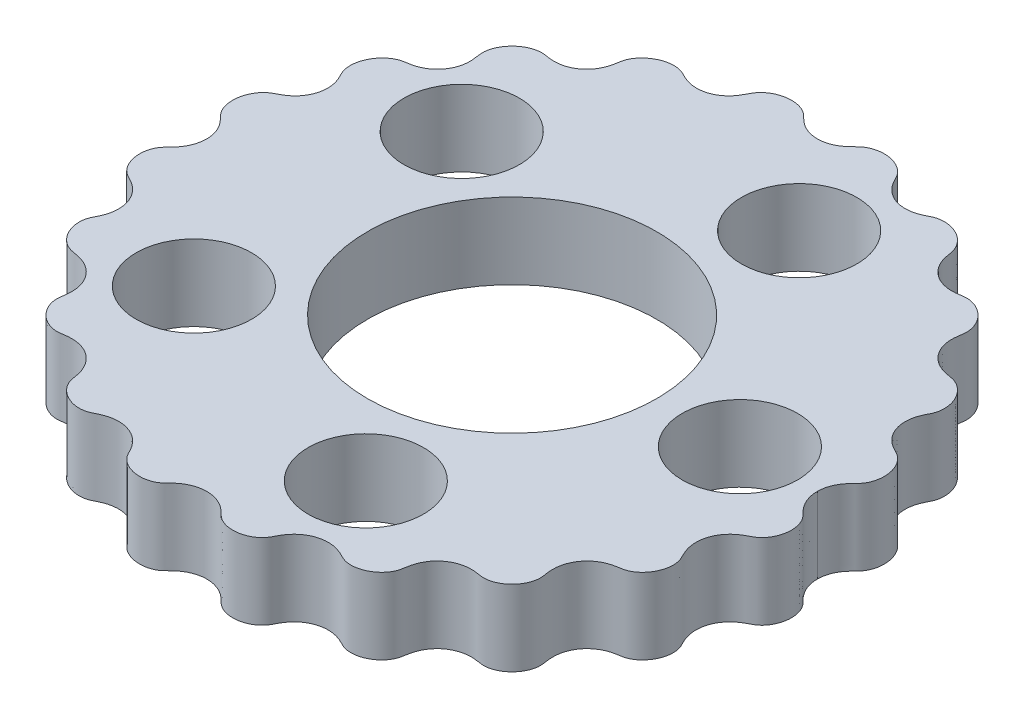
SolidWorks part; units mm, degrees
ref_plane "Front Plane" through (0, 0, 0) normal (0, 0, 1) x (1, 0, 0)
ref_plane "Top Plane" through (0, 0, 0) normal (0, 1, 0) x (1, 0, 0)
ref_plane "Right Plane" through (0, 0, 0) normal (1, 0, 0) x (0, 0, -1)
sketch "MAIN" plane through (0, 0, 0) normal (0, 1, 0) x (1, 0, 0)
  line L0 (-20.1, 0) -> (20.1, 0) construction
  line L1 (0, 0) -> (-0.8, 0)
  line L4 (0, -20.1) -> (0, 20.1) construction
  line L5 (-0.8, -20.2489) -> (-0.8, 20.2572) construction
  circle A22 centre (0, 0) radius 15
  circle A23 centre (15, 0) radius 3.8
  circle A24 centre (4.6353, -14.2658) radius 3.8
  circle A25 centre (-12.1353, -8.8168) radius 3.8
  circle A26 centre (-12.1353, 8.8168) radius 3.8
  circle A27 centre (4.6353, 14.2658) radius 3.8
  circle A29 centre (0, 0) radius 9.525
  spline S0 degree 4 poles (20.5886, 4.7068) (20.68, 4.6551) (20.8532, 4.5348) (21.1393, 4.2364) (21.3748, 3.7649) (21.4816, 3.2447) (21.4517, 2.7569) (21.3623, 2.4139) (21.2306, 2.1338) (21.0766, 1.9171) (20.8954, 1.7433) (20.7304, 1.5739) (20.553, 1.3627) (20.4068, 1.1453) (20.2874, 0.911) (20.1977, 0.6657) (20.1512, 0.4864) (20.1234, 0.3358) (20.1091, 0.21) (20.1026, 0.1123) (20.0996, 0.0252) (20.0999, -0.045) (20.1041, -0.1445) (20.1129, -0.2489) (20.1295, -0.3715) (20.1582, -0.5159) (20.2042, -0.6849) (20.2735, -0.8706) (20.3588, -1.0503) (20.459, -1.2218) (20.5666, -1.3754) (20.6778, -1.5121) (20.7891, -1.634) (20.8973, -1.7433) (21.0065, -1.8517) (21.1088, -1.9667) (21.2202, -2.1239) (21.3466, -2.3693) (21.4488, -2.7149) (21.4796, -3.1509) (21.4067, -3.6189) (21.2535, -4.0101) (21.0548, -4.3168) (20.8346, -4.5468) (20.6123, -4.7043) (20.3253, -4.8398) (20.0085, -5.0187) (19.6843, -5.2734) (19.3864, -5.6226) (19.1654, -6.0238) (19.0313, -6.4606) (18.9938, -6.8578) (19.019, -7.1969) (19.0763, -7.4737) (19.1428, -7.6897) (19.2312, -7.9077) (19.34, -8.1256) (19.4583, -8.3497) (19.5343, -8.602) (19.5712, -8.9102) (19.5475, -9.2683) (19.4413, -9.6634) (19.2307, -10.0711) (18.9626, -10.3939) (18.6946, -10.6074) (18.4633, -10.7327) (18.291, -10.7987) (18.1484, -10.8366) (18.0032, -10.862) (17.8576, -10.8843) (17.6411, -10.9233) (17.3574, -10.9968) (17.0179, -11.137) (16.6499, -11.3793) (16.3344, -11.6905) (16.085, -12.0601) (15.9134, -12.4744) (15.8373, -12.8617) (15.8261, -13.1985) (15.849, -13.4869) (15.8867, -13.7254) (15.9272, -13.9735) (15.9178, -14.2345) (15.8554, -14.5357) (15.7209, -14.8652) (15.4941, -15.2104) (15.1574, -15.5384) (14.7814, -15.7682) (14.4318, -15.8866) (14.1468, -15.9236) (13.9404, -15.918) (13.777, -15.8957) (13.5739, -15.8619) (13.3114, -15.8302) (12.9878, -15.8261) (12.6091, -15.8813) (12.2295, -16.0072) (11.877, -16.1993) (11.5634, -16.4525) (11.2997, -16.7592) (11.0942, -17.1092) (10.963, -17.4616) (10.8972, -17.764) (10.8626, -18.0051) (10.8228, -18.2154) (10.7561, -18.4196) (10.6183, -18.6831) (10.379, -18.9781) (10.0502, -19.2452) (9.6329, -19.4535) (9.2235, -19.5558) (8.8836, -19.5696) (8.6248, -19.5345) (8.4481, -19.4868) (8.3117, -19.4338) (8.1804, -19.3695) (8.0505, -19.3025) (7.8489, -19.2051) (7.5676, -19.0948) (7.1959, -19.0078) (6.7361, -18.9938) (6.2861, -19.0732) (5.8648, -19.241) (5.4886, -19.4879) (5.2101, -19.7619) (5.0117, -20.0304) (4.884, -20.2493) (4.8047, -20.4037) (4.7227, -20.5647) (4.6271, -20.7269) (4.4866, -20.8967) (4.2614, -21.0946) (3.9625, -21.275) (3.5833, -21.4148) (3.129, -21.4789) (2.7059, -21.4461) (2.3697, -21.3462) (2.1288, -21.223) (1.9722, -21.1131) (1.8575, -21.0121) (1.7229, -20.8767) (1.5347, -20.6912) (1.271, -20.4785) (0.9112, -20.275) (0.4846, -20.1344) (0.0431, -20.0821) (-0.3958, -20.1176) (-0.8148, -20.2365) (-1.152, -20.4058) (-1.4146, -20.5926) (-1.6227, -20.7757) (-1.7854, -20.9409) (-1.9581, -21.1102) (-2.1683, -21.2484) (-2.4378, -21.3695) (-2.7687, -21.4523) (-3.1582, -21.4754) (-3.5925, -21.4114) (-3.9625, -21.275) (-4.2614, -21.0946) (-4.4866, -20.8967) (-4.6271, -20.7269) (-4.7227, -20.5647) (-4.8047, -20.4037) (-4.884, -20.2493) (-5.0117, -20.0304) (-5.2101, -19.7619) (-5.4886, -19.4879) (-5.8648, -19.241) (-6.2861, -19.0732) (-6.7361, -18.9938) (-7.1959, -19.0078) (-7.5676, -19.0948) (-7.8489, -19.2051) (-8.0505, -19.3025) (-8.1804, -19.3695) (-8.3117, -19.4338) (-8.4481, -19.4868) (-8.6248, -19.5345) (-8.8836, -19.5696) (-9.2235, -19.5558) (-9.6329, -19.4535) (-10.0502, -19.2452) (-10.379, -18.9781) (-10.6183, -18.6831) (-10.7561, -18.4196) (-10.8228, -18.2154) (-10.8561, -18.0402) (-10.8777, -17.8992) (-10.9125, -17.6942) (-10.9754, -17.428) (-11.0942, -17.1093) (-11.2996, -16.7592) (-11.5634, -16.4525) (-11.877, -16.1993) (-12.2295, -16.0072) (-12.6091, -15.8813) (-12.9878, -15.8261) (-13.3114, -15.8302) (-13.5739, -15.8619) (-13.777, -15.8957) (-13.9404, -15.918) (-14.1468, -15.9236) (-14.4318, -15.8866) (-14.7814, -15.7682) (-15.1574, -15.5384) (-15.4941, -15.2104) (-15.7209, -14.8652) (-15.8554, -14.5357) (-15.9178, -14.2345) (-15.9272, -13.9735) (-15.8867, -13.7254) (-15.849, -13.4869) (-15.8261, -13.1985) (-15.8373, -12.8617) (-15.9134, -12.4744) (-16.085, -12.0601) (-16.3344, -11.6905) (-16.6499, -11.3793) (-17.0179, -11.137) (-17.3574, -10.9968) (-17.6411, -10.9233) (-17.8576, -10.8843) (-18.0032, -10.862) (-18.1484, -10.8366) (-18.291, -10.7987) (-18.4633, -10.7327) (-18.6946, -10.6074) (-18.9626, -10.3939) (-19.2307, -10.0711) (-19.4413, -9.6634) (-19.5475, -9.2683) (-19.5712, -8.9102) (-19.5343, -8.602) (-19.4583, -8.3497) (-19.34, -8.1256) (-19.2312, -7.9077) (-19.1215, -7.6374) (-19.0312, -7.3099) (-18.9886, -6.9144) (-19.0312, -6.4607) (-19.1654, -6.0238) (-19.3864, -5.6226) (-19.6843, -5.2734) (-20.0085, -5.0187) (-20.3253, -4.8398) (-20.6123, -4.7043) (-20.8346, -4.5468) (-21.0548, -4.3168) (-21.2535, -4.0101) (-21.4067, -3.6189) (-21.4796, -3.1509) (-21.4488, -2.7149) (-21.3466, -2.3693) (-21.2202, -2.1239) (-21.1088, -1.9667) (-21.0065, -1.8517) (-20.8973, -1.7433) (-20.7891, -1.634) (-20.6778, -1.5121) (-20.5666, -1.3754) (-20.459, -1.2218) (-20.3588, -1.0503) (-20.2735, -0.8706) (-20.2042, -0.6849) (-20.1582, -0.5159) (-20.1295, -0.3715) (-20.1129, -0.2489) (-20.1041, -0.1442) (-20.099, -0.0256) (-20.0999, 0.0597) (-20.107, 0.1917) (-20.1234, 0.3359) (-20.1512, 0.4864) (-20.1977, 0.6656) (-20.2874, 0.9112) (-20.4306, 1.1918) (-20.6222, 1.4599) (-20.8576, 1.7072) (-21.0766, 1.917) (-21.2306, 2.1338) (-21.3623, 2.4139) (-21.4517, 2.7569) (-21.4816, 3.2446) (-21.3748, 3.7649) (-21.1393, 4.2364) (-20.8532, 4.5348) (-20.68, 4.6551) (-20.5886, 4.7068) knots 0 0 0 0 0 0.004854 0.009708 0.018897 0.023991 0.029085 0.03214 0.035194 0.038248 0.041303 0.043723 0.046143 0.050984 0.053404 0.055825 0.058245 0.059455 0.060665 0.061539 0.062412 0.06356 0.064708 0.065855 0.067003 0.069298 0.071593 0.073888 0.076184 0.078479 0.080774 0.082553 0.084332 0.086111 0.08789 0.089668 0.091447 0.095005 0.100606 0.106208 0.111478 0.116748 0.119878 0.123007 0.126137 0.129267 0.13454 0.139813 0.145086 0.150359 0.155581 0.160804 0.163415 0.166026 0.168637 0.171249 0.174275 0.177302 0.180329 0.183356 0.188577 0.193798 0.19911 0.204423 0.207831 0.209535 0.211238 0.212942 0.214646 0.21635 0.218053 0.223116 0.228179 0.233242 0.238305 0.243486 0.248667 0.253849 0.25644 0.25903 0.262031 0.265031 0.268031 0.271032 0.27621 0.281388 0.286995 0.292602 0.296412 0.298318 0.300223 0.302128 0.304034 0.307844 0.312446 0.317047 0.321648 0.32625 0.330919 0.335589 0.340258 0.344928 0.348227 0.349876 0.351526 0.354825 0.358123 0.363551 0.368978 0.374256 0.379533 0.382914 0.384604 0.386294 0.387984 0.389675 0.391365 0.393055 0.39834 0.403624 0.408909 0.414194 0.419326 0.424458 0.429589 0.432155 0.434721 0.43617 0.437618 0.440515 0.443412 0.44631 0.451439 0.456568 0.46197 0.467372 0.470904 0.47267 0.474436 0.476202 0.477968 0.4815 0.486659 0.491818 0.496977 0.502136 0.507093 0.51205 0.517007 0.519485 0.521964 0.524855 0.527745 0.530636 0.533527 0.538479 0.543432 0.548561 0.55369 0.556588 0.559485 0.562382 0.56383 0.565279 0.567845 0.570411 0.575542 0.580674 0.585806 0.591091 0.596376 0.60166 0.606945 0.608635 0.610325 0.612016 0.613706 0.615396 0.617086 0.620467 0.625744 0.631022 0.636449 0.641877 0.645175 0.648474 0.650124 0.651773 0.653423 0.655072 0.659742 0.664411 0.669081 0.67375 0.678352 0.682953 0.687554 0.692156 0.695966 0.697872 0.699777 0.701682 0.703588 0.707398 0.713005 0.718612 0.72379 0.728968 0.731969 0.734969 0.737969 0.74097 0.74356 0.746151 0.751333 0.756514 0.761695 0.766758 0.771821 0.776884 0.781947 0.78365 0.785354 0.787058 0.788762 0.790465 0.792169 0.795577 0.80089 0.806202 0.811423 0.816644 0.819671 0.822698 0.825725 0.828751 0.831363 0.833974 0.839196 0.844419 0.849641 0.854914 0.860187 0.86546 0.870733 0.873863 0.876993 0.880122 0.883252 0.888522 0.893792 0.899394 0.904995 0.908553 0.910332 0.91211 0.913889 0.915668 0.917447 0.919226 0.921521 0.923816 0.926112 0.928407 0.930702 0.932997 0.934145 0.935292 0.93644 0.937588 0.939335 0.940545 0.941755 0.944175 0.946596 0.949016 0.953857 0.958697 0.961752 0.964806 0.96786 0.970915 0.976009 0.981103 0.990292 0.995146 1 1 1 1 1 construction
  spline S1 degree 4 poles (20.1, 0) (20.1, -0.0217) (20.1007, -0.0652) (20.1041, -0.1445) (20.1129, -0.2489) (20.1295, -0.3715) (20.1582, -0.5159) (20.2042, -0.6849) (20.2735, -0.8706) (20.3588, -1.0503) (20.459, -1.2218) (20.5666, -1.3754) (20.6778, -1.5121) (20.7891, -1.634) (20.8973, -1.7433) (21.0065, -1.8517) (21.1088, -1.9667) (21.2202, -2.1239) (21.3466, -2.3693) (21.4488, -2.7149) (21.4796, -3.1509) (21.4067, -3.6189) (21.2535, -4.0101) (21.0548, -4.3168) (20.8346, -4.5468) (20.6123, -4.7043) (20.3253, -4.8398) (20.0085, -5.0187) (19.6843, -5.2734) (19.3864, -5.6226) (19.1654, -6.0238) (19.0313, -6.4606) (18.9938, -6.8578) (19.019, -7.1969) (19.0763, -7.4737) (19.1428, -7.6897) (19.2312, -7.9077) (19.34, -8.1256) (19.4583, -8.3497) (19.5343, -8.602) (19.5712, -8.9102) (19.5475, -9.2683) (19.4413, -9.6634) (19.2307, -10.0711) (18.9626, -10.3939) (18.6946, -10.6074) (18.4633, -10.7327) (18.291, -10.7987) (18.1484, -10.8366) (18.0032, -10.862) (17.8576, -10.8843) (17.6411, -10.9233) (17.3574, -10.9968) (17.0179, -11.137) (16.6499, -11.3793) (16.3344, -11.6905) (16.085, -12.0601) (15.9134, -12.4744) (15.8373, -12.8617) (15.8261, -13.1985) (15.849, -13.4869) (15.8867, -13.7254) (15.9272, -13.9735) (15.9178, -14.2345) (15.8554, -14.5357) (15.7209, -14.8652) (15.4941, -15.2104) (15.1574, -15.5384) (14.7814, -15.7682) (14.4318, -15.8866) (14.1468, -15.9236) (13.9404, -15.918) (13.777, -15.8957) (13.5739, -15.8619) (13.3114, -15.8302) (12.9878, -15.8261) (12.6091, -15.8813) (12.2295, -16.0072) (11.877, -16.1993) (11.5634, -16.4525) (11.2997, -16.7592) (11.0942, -17.1092) (10.963, -17.4616) (10.8972, -17.764) (10.8626, -18.0051) (10.8228, -18.2154) (10.7561, -18.4196) (10.6183, -18.6831) (10.379, -18.9781) (10.0502, -19.2452) (9.6329, -19.4535) (9.2235, -19.5558) (8.8836, -19.5696) (8.6248, -19.5345) (8.4481, -19.4868) (8.3117, -19.4338) (8.1804, -19.3695) (8.0505, -19.3025) (7.8489, -19.2051) (7.5676, -19.0948) (7.1959, -19.0078) (6.7361, -18.9938) (6.2861, -19.0732) (5.8648, -19.241) (5.4886, -19.4879) (5.2101, -19.7619) (5.0117, -20.0304) (4.884, -20.2493) (4.8047, -20.4037) (4.7227, -20.5647) (4.6271, -20.7269) (4.4866, -20.8967) (4.2614, -21.0946) (3.9625, -21.275) (3.5833, -21.4148) (3.129, -21.4789) (2.7059, -21.4461) (2.3697, -21.3462) (2.1288, -21.223) (1.9722, -21.1131) (1.8575, -21.0121) (1.7229, -20.8767) (1.5347, -20.6912) (1.271, -20.4785) (0.9112, -20.275) (0.4846, -20.1344) (0.0431, -20.0821) (-0.3958, -20.1176) (-0.8148, -20.2365) (-1.152, -20.4058) (-1.4146, -20.5926) (-1.6227, -20.7757) (-1.7854, -20.9409) (-1.9581, -21.1102) (-2.1683, -21.2484) (-2.4378, -21.3695) (-2.7687, -21.4523) (-3.1582, -21.4754) (-3.5925, -21.4114) (-3.9625, -21.275) (-4.2614, -21.0946) (-4.4866, -20.8967) (-4.6271, -20.7269) (-4.7227, -20.5647) (-4.8047, -20.4037) (-4.884, -20.2493) (-5.0117, -20.0304) (-5.2101, -19.7619) (-5.4886, -19.4879) (-5.8648, -19.241) (-6.2861, -19.0732) (-6.7361, -18.9938) (-7.1959, -19.0078) (-7.5676, -19.0948) (-7.8489, -19.2051) (-8.0505, -19.3025) (-8.1804, -19.3695) (-8.3117, -19.4338) (-8.4481, -19.4868) (-8.6248, -19.5345) (-8.8836, -19.5696) (-9.2235, -19.5558) (-9.6329, -19.4535) (-10.0502, -19.2452) (-10.379, -18.9781) (-10.6183, -18.6831) (-10.7561, -18.4196) (-10.8228, -18.2154) (-10.8561, -18.0402) (-10.8777, -17.8992) (-10.9125, -17.6942) (-10.9754, -17.428) (-11.0942, -17.1093) (-11.2996, -16.7592) (-11.5634, -16.4525) (-11.877, -16.1993) (-12.2295, -16.0072) (-12.6091, -15.8813) (-12.9878, -15.8261) (-13.3114, -15.8302) (-13.5739, -15.8619) (-13.777, -15.8957) (-13.9404, -15.918) (-14.1468, -15.9236) (-14.4318, -15.8866) (-14.7814, -15.7682) (-15.1574, -15.5384) (-15.4941, -15.2104) (-15.7209, -14.8652) (-15.8554, -14.5357) (-15.9178, -14.2345) (-15.9272, -13.9735) (-15.8867, -13.7254) (-15.849, -13.4869) (-15.8261, -13.1985) (-15.8373, -12.8617) (-15.9134, -12.4744) (-16.085, -12.0601) (-16.3344, -11.6905) (-16.6499, -11.3793) (-17.0179, -11.137) (-17.3574, -10.9968) (-17.6411, -10.9233) (-17.8576, -10.8843) (-18.0032, -10.862) (-18.1484, -10.8366) (-18.291, -10.7987) (-18.4633, -10.7327) (-18.6946, -10.6074) (-18.9626, -10.3939) (-19.2307, -10.0711) (-19.4413, -9.6634) (-19.5475, -9.2683) (-19.5712, -8.9102) (-19.5343, -8.602) (-19.4583, -8.3497) (-19.34, -8.1256) (-19.2312, -7.9077) (-19.1215, -7.6374) (-19.0312, -7.3099) (-18.9886, -6.9144) (-19.0312, -6.4607) (-19.1654, -6.0238) (-19.3864, -5.6226) (-19.6843, -5.2734) (-20.0085, -5.0187) (-20.3253, -4.8398) (-20.6123, -4.7043) (-20.8346, -4.5468) (-21.0548, -4.3168) (-21.2535, -4.0101) (-21.4067, -3.6189) (-21.4796, -3.1509) (-21.4488, -2.7149) (-21.3466, -2.3693) (-21.2202, -2.1239) (-21.1088, -1.9667) (-21.0065, -1.8517) (-20.8973, -1.7433) (-20.7891, -1.634) (-20.6778, -1.5121) (-20.5666, -1.3754) (-20.459, -1.2218) (-20.3588, -1.0503) (-20.2735, -0.8706) (-20.2042, -0.6849) (-20.1582, -0.5159) (-20.1295, -0.3715) (-20.1129, -0.2489) (-20.1041, -0.1442) (-20.1007, -0.0655) (-20.1, -0.0217) (-20.1, 0) knots 0.062412 0.062412 0.062412 0.062412 0.062412 0.06356 0.064708 0.065855 0.067003 0.069298 0.071593 0.073888 0.076184 0.078479 0.080774 0.082553 0.084332 0.086111 0.08789 0.089668 0.091447 0.095005 0.100606 0.106208 0.111478 0.116748 0.119878 0.123007 0.126137 0.129267 0.13454 0.139813 0.145086 0.150359 0.155581 0.160804 0.163415 0.166026 0.168637 0.171249 0.174275 0.177302 0.180329 0.183356 0.188577 0.193798 0.19911 0.204423 0.207831 0.209535 0.211238 0.212942 0.214646 0.21635 0.218053 0.223116 0.228179 0.233242 0.238305 0.243486 0.248667 0.253849 0.25644 0.25903 0.262031 0.265031 0.268031 0.271032 0.27621 0.281388 0.286995 0.292602 0.296412 0.298318 0.300223 0.302128 0.304034 0.307844 0.312446 0.317047 0.321648 0.32625 0.330919 0.335589 0.340258 0.344928 0.348227 0.349876 0.351526 0.354825 0.358123 0.363551 0.368978 0.374256 0.379533 0.382914 0.384604 0.386294 0.387984 0.389675 0.391365 0.393055 0.39834 0.403624 0.408909 0.414194 0.419326 0.424458 0.429589 0.432155 0.434721 0.43617 0.437618 0.440515 0.443412 0.44631 0.451439 0.456568 0.46197 0.467372 0.470904 0.47267 0.474436 0.476202 0.477968 0.4815 0.486659 0.491818 0.496977 0.502136 0.507093 0.51205 0.517007 0.519485 0.521964 0.524855 0.527745 0.530636 0.533527 0.538479 0.543432 0.548561 0.55369 0.556588 0.559485 0.562382 0.56383 0.565279 0.567845 0.570411 0.575542 0.580674 0.585806 0.591091 0.596376 0.60166 0.606945 0.608635 0.610325 0.612016 0.613706 0.615396 0.617086 0.620467 0.625744 0.631022 0.636449 0.641877 0.645175 0.648474 0.650124 0.651773 0.653423 0.655072 0.659742 0.664411 0.669081 0.67375 0.678352 0.682953 0.687554 0.692156 0.695966 0.697872 0.699777 0.701682 0.703588 0.707398 0.713005 0.718612 0.72379 0.728968 0.731969 0.734969 0.737969 0.74097 0.74356 0.746151 0.751333 0.756514 0.761695 0.766758 0.771821 0.776884 0.781947 0.78365 0.785354 0.787058 0.788762 0.790465 0.792169 0.795577 0.80089 0.806202 0.811423 0.816644 0.819671 0.822698 0.825725 0.828751 0.831363 0.833974 0.839196 0.844419 0.849641 0.854914 0.860187 0.86546 0.870733 0.873863 0.876993 0.880122 0.883252 0.888522 0.893792 0.899394 0.904995 0.908553 0.910332 0.91211 0.913889 0.915668 0.917447 0.919226 0.921521 0.923816 0.926112 0.928407 0.930702 0.932997 0.934145 0.935292 0.93644 0.937588 0.937588 0.937588 0.937588 0.937588
  spline S2 degree 4 poles (20.1, 0) (20.1, 0.016) (20.1004, 0.0483) (20.103, 0.1222) (20.112, 0.2418) (20.1299, 0.3658) (20.1605, 0.5103) (20.2009, 0.6519) (20.2511, 0.7903) (20.3105, 0.925) (20.405, 1.1055) (20.5226, 1.2843) (20.6637, 1.4579) (20.8251, 1.6262) (20.9585, 1.7565) (21.084, 1.8949) (21.1907, 2.0485) (21.3222, 2.2956) (21.4364, 2.6526) (21.4803, 3.1177) (21.4039, 3.6005) (21.2554, 3.9885) (21.0881, 4.2662) (20.9406, 4.4515) (20.7839, 4.6031) (20.6242, 4.7228) (20.4498, 4.8192) (20.2714, 4.9072) (20.0538, 5.0278) (19.7727, 5.2201) (19.4603, 5.5221) (19.1704, 5.9791) (19.0001, 6.551) (18.9968, 7.0935) (19.1004, 7.5221) (19.226, 7.825) (19.3231, 8.0197) (19.4032, 8.1742) (19.4892, 8.3744) (19.5665, 8.6825) (19.5779, 9.1011) (19.4647, 9.6109) (19.2312, 10.0617) (18.9516, 10.3963) (18.6873, 10.6122) (18.4786, 10.7388) (18.2767, 10.8266) (18.088, 10.8805) (17.8946, 10.9117) (17.7013, 10.9419) (17.5098, 10.9831) (17.3219, 11.0382) (17.0549, 11.141) (16.7249, 11.3247) (16.3639, 11.6361) (16.0441, 12.1125) (15.8775, 12.6141) (15.841, 13.046) (15.8658, 13.3784) (15.9011, 13.611) (15.9319, 13.7968) (15.9482, 14.0321) (15.9148, 14.3537) (15.7871, 14.7447) (15.5207, 15.1776) (15.173, 15.5163) (14.8159, 15.7409) (14.503, 15.8642) (14.2676, 15.9213) (14.0488, 15.9441) (13.8511, 15.9387) (13.6559, 15.909) (13.4613, 15.8774) (13.265, 15.8568) (13.0677, 15.8506) (12.7762, 15.8657) (12.3956, 15.941) (11.9386, 16.1371) (11.4706, 16.5199) (11.1629, 16.9705) (11.0089, 17.3828) (10.9417, 17.7007) (10.9094, 17.9106) (10.8813, 18.0783) (10.8259, 18.2838) (10.7008, 18.5665) (10.4632, 18.8965) (10.1065, 19.2033) (9.6723, 19.4296) (9.2327, 19.5511) (8.8627, 19.5763) (8.5739, 19.5408) (8.3713, 19.483) (8.2335, 19.4293) (8.1088, 19.3698) (7.9719, 19.2984) (7.8178, 19.2242) (7.6203, 19.1423) (7.3752, 19.0655) (7.0593, 19.0086) (6.6743, 19.0056) (6.2349, 19.0853) (5.7672, 19.2865) (5.3804, 19.5853) (5.1146, 19.9125) (4.9536, 20.1837) (4.8383, 20.4088) (4.7236, 20.6354) (4.5008, 20.9158) (4.1338, 21.1948) (3.6506, 21.4015) (3.1414, 21.4742) (2.7011, 21.4391) (2.3677, 21.3457) (2.1404, 21.2452) (1.9708, 21.1395) (1.8527, 21.0456) (1.7606, 20.9601) (1.6892, 20.8895) (1.6182, 20.8184) (1.546, 20.7486) (1.4535, 20.6637) (1.3379, 20.5669) (1.1957, 20.4632) (0.9444, 20.3112) (0.5869, 20.1608) (0.0974, 20.0677) (-0.5067, 20.1237) (-1.0106, 20.3249) (-1.3647, 20.5768) (-1.5935, 20.7925) (-1.7318, 20.9329) (-1.8462, 21.0415) (-2.0019, 21.1628) (-2.2547, 21.308) (-2.6214, 21.4316) (-3.112, 21.4794) (-3.6642, 21.3957) (-4.1338, 21.1948) (-4.5008, 20.9158) (-4.7236, 20.6354) (-4.8383, 20.4088) (-4.9536, 20.1837) (-5.1146, 19.9125) (-5.3804, 19.5853) (-5.7672, 19.2865) (-6.2349, 19.0853) (-6.6743, 19.0056) (-7.0593, 19.0086) (-7.3752, 19.0655) (-7.6203, 19.1423) (-7.8178, 19.2242) (-7.9719, 19.2984) (-8.1088, 19.3698) (-8.2335, 19.4293) (-8.3713, 19.483) (-8.5739, 19.5408) (-8.8627, 19.5763) (-9.2327, 19.5511) (-9.6723, 19.4296) (-10.1065, 19.2033) (-10.4632, 18.8965) (-10.7008, 18.5665) (-10.8259, 18.2838) (-10.8813, 18.0783) (-10.9094, 17.9106) (-10.9417, 17.7007) (-11.0089, 17.3828) (-11.1629, 16.9705) (-11.4705, 16.5199) (-11.9386, 16.1371) (-12.4415, 15.9213) (-12.8743, 15.8493) (-13.2159, 15.8516) (-13.4613, 15.8774) (-13.6559, 15.909) (-13.8511, 15.9387) (-14.0488, 15.9441) (-14.2676, 15.9213) (-14.503, 15.8642) (-14.8159, 15.7409) (-15.173, 15.5163) (-15.5207, 15.1776) (-15.7871, 14.7447) (-15.9148, 14.3537) (-15.9482, 14.0321) (-15.9319, 13.7968) (-15.9011, 13.611) (-15.8658, 13.3784) (-15.841, 13.046) (-15.8775, 12.6141) (-16.0441, 12.1125) (-16.3639, 11.6361) (-16.7249, 11.3247) (-17.0549, 11.141) (-17.3219, 11.0382) (-17.5098, 10.9831) (-17.7013, 10.9419) (-17.8946, 10.9117) (-18.088, 10.8805) (-18.2767, 10.8266) (-18.4786, 10.7388) (-18.6873, 10.6122) (-18.9516, 10.3963) (-19.2312, 10.0617) (-19.4647, 9.6109) (-19.5779, 9.1011) (-19.5665, 8.6825) (-19.4892, 8.3744) (-19.4032, 8.1742) (-19.3231, 8.0197) (-19.226, 7.825) (-19.1004, 7.5221) (-18.9968, 7.0935) (-19.0001, 6.551) (-19.1704, 5.9791) (-19.4603, 5.5221) (-19.7727, 5.2201) (-20.0538, 5.0278) (-20.2714, 4.9072) (-20.4498, 4.8192) (-20.6242, 4.7228) (-20.7839, 4.6031) (-20.9406, 4.4515) (-21.0881, 4.2662) (-21.2554, 3.9885) (-21.4039, 3.6005) (-21.4803, 3.1177) (-21.4364, 2.6526) (-21.3222, 2.2956) (-21.1907, 2.0485) (-21.084, 1.8949) (-20.9585, 1.7565) (-20.8251, 1.6262) (-20.6637, 1.4579) (-20.5226, 1.2843) (-20.405, 1.1055) (-20.3105, 0.925) (-20.2511, 0.7903) (-20.2009, 0.6519) (-20.1605, 0.5103) (-20.1299, 0.3658) (-20.112, 0.2419) (-20.103, 0.1218) (-20.1004, 0.0485) (-20.1, 0.016) (-20.1, 0) knots 0.063609 0.063609 0.063609 0.063609 0.063609 0.064458 0.065307 0.067005 0.068703 0.070402 0.0721 0.073798 0.075496 0.077194 0.0815 0.083653 0.085806 0.087958 0.090111 0.092264 0.094417 0.100851 0.107286 0.113599 0.116755 0.119912 0.122208 0.124504 0.1268 0.129096 0.131392 0.133688 0.13828 0.144787 0.151294 0.158382 0.16547 0.169487 0.171496 0.173504 0.175513 0.177521 0.181538 0.188089 0.19464 0.201359 0.204718 0.208078 0.210337 0.212596 0.214854 0.217113 0.219372 0.221631 0.22389 0.226149 0.232563 0.238978 0.24565 0.252321 0.256667 0.25884 0.261013 0.263186 0.265358 0.269704 0.275849 0.281993 0.288591 0.29189 0.295189 0.297466 0.299742 0.302018 0.304295 0.306571 0.308848 0.311124 0.3134 0.320031 0.326662 0.333804 0.340946 0.344869 0.34683 0.348792 0.350753 0.352715 0.356638 0.362993 0.369347 0.374207 0.379066 0.383919 0.386345 0.387558 0.388771 0.390744 0.392717 0.39469 0.396663 0.400609 0.404555 0.40945 0.414345 0.42109 0.427836 0.431732 0.433681 0.435629 0.439525 0.443422 0.450062 0.456701 0.463502 0.466903 0.470303 0.472622 0.474941 0.476101 0.47726 0.47842 0.479579 0.480739 0.481898 0.484217 0.486536 0.488855 0.49544 0.502026 0.50926 0.516494 0.520133 0.521952 0.523772 0.525591 0.527411 0.53105 0.537174 0.543299 0.549938 0.556578 0.560475 0.564371 0.566319 0.568268 0.572164 0.57891 0.585655 0.59055 0.595445 0.599391 0.603337 0.60531 0.607283 0.609256 0.611229 0.612442 0.613655 0.616081 0.620934 0.625793 0.630653 0.637007 0.643362 0.647285 0.649247 0.651208 0.65317 0.655131 0.659054 0.666196 0.673338 0.679969 0.6866 0.691152 0.693429 0.695705 0.697982 0.700258 0.702534 0.704811 0.70811 0.711409 0.718007 0.724151 0.730296 0.734642 0.736814 0.738987 0.74116 0.743333 0.747679 0.75435 0.761022 0.767437 0.773851 0.77611 0.778369 0.780628 0.782887 0.785146 0.787404 0.789663 0.791922 0.795282 0.798641 0.80536 0.811911 0.818462 0.822479 0.824487 0.826496 0.828504 0.830513 0.83453 0.841618 0.848706 0.855213 0.86172 0.866312 0.868608 0.870904 0.8732 0.875496 0.877792 0.880088 0.883245 0.886401 0.892714 0.899149 0.905583 0.907736 0.909889 0.912042 0.914194 0.916347 0.9185 0.922806 0.924504 0.926202 0.9279 0.929598 0.931297 0.932995 0.934693 0.935542 0.936391 0.936391 0.936391 0.936391 0.936391
  point P67 (0, 0)
  dimension "D1" = 19.05
  dimension "D4" = 30
  dimension "D5" = 7.6
  dimension "D6" = 5
extrude "Boss-Extrude1" add sketch "MAIN" along normal blind 5 from offset 0.5 contours S1 S2 A27 A22 A23 A24 A25 A26 | A27 A22 A26 A25 A24 A23 A29 region at (10.7791, 0, 0) region at (0, 0, 19.4931)
